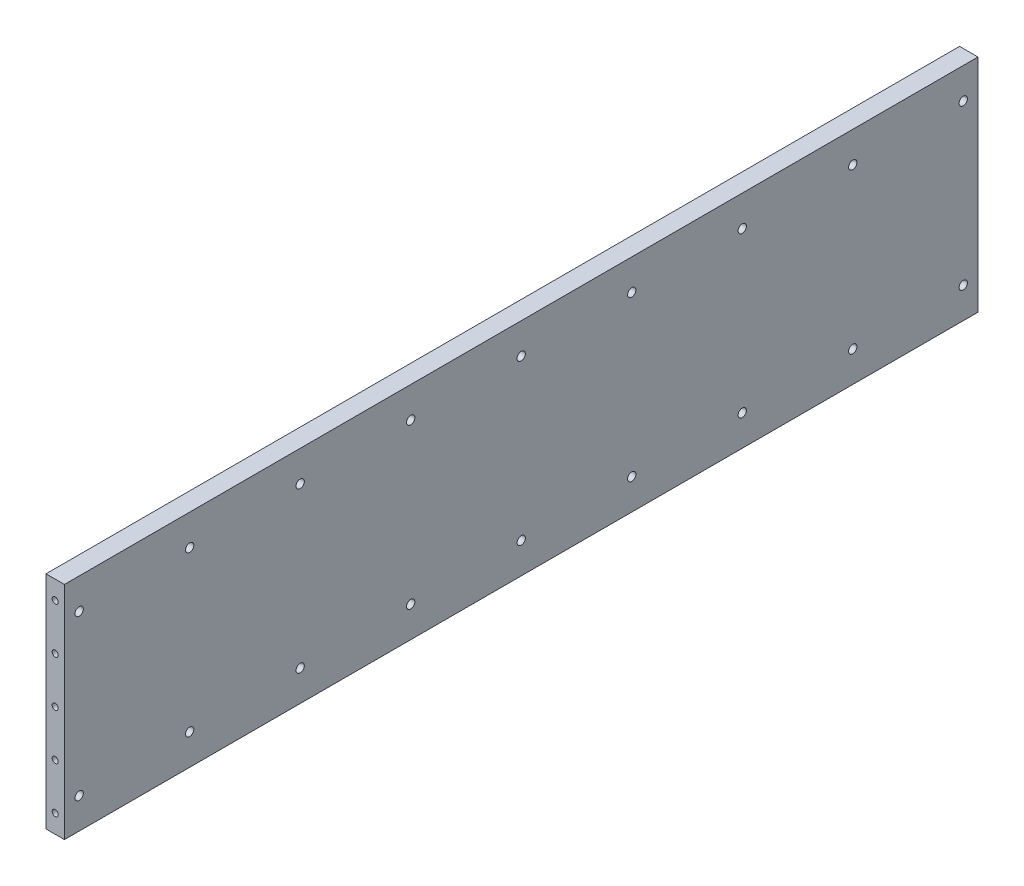
SolidWorks part; units mm, degrees
ref_plane "Front Plane" through (0, 0, 0) normal (0, 0, 1) x (1, 0, 0)
ref_plane "Top Plane" through (0, 0, 0) normal (0, 1, 0) x (1, 0, 0)
ref_plane "Right Plane" through (0, 0, 0) normal (1, 0, 0) x (0, 0, -1)
sketch "Sketch2" plane through (0, 0, 0) normal (0, 0, 1) x (1, 0, 0)
  line L0 (-10, 0) -> (0, 0)
  line L3 (0, 0) -> (0, -120)
  line L4 (0, -120) -> (-10, -120)
  line L5 (-10, -120) -> (-10, 0)
  dimension "D1" = 120
  dimension "D2" = 10
extrude "Boss-Extrude1" add sketch "Sketch2" along normal blind 496
sketch "Sketch3" plane through (0, 0, 496) normal (0, 0, 1) x (1, 0, 0)
  line L0 (-5, 0) -> (-5, -120) construction
  line L1 (0, 0) -> (-10, 0) construction
  line L2 (-10, -120) -> (0, -120) construction
  line L3 (-10, -60) -> (0, -60) construction
  line L4 (-10, 0) -> (-10, -120) construction
  line L5 (0, -120) -> (0, 0) construction
  point P12 (-5, -60)
  point P13 (-5, -110)
  point P14 (-5, -35)
  point P15 (-5, -10)
  point P16 (-5, -85)
  dimension "D1" = 3
hole_wizard "M4 Tapped Hole1" positions "3DSketch1" profile "Sketch4" tap size "M4" standard "ISO"
sketch3d "3DSketch1"
  point P0 (-5, -10, 496)
  point P3 (-5, -35, 496)
  point P6 (-5, -60, 496)
  point P9 (-5, -85, 496)
  point P12 (-5, -110, 496)
sketch "Sketch4" plane through (-5, -10, 496) normal (1, 0, 0) x (0, -1, 0)
  line L0 (0, 0) -> (0, 15.0914)
  line L1 (0, 15.0914) -> (1.65, 14.1)
  line L2 (1.65, 14.1) -> (1.65, 0)
  line L5 (1.65, 0) -> (0, 0)
  line L10 (0, 15.0914) -> (-1.65, 14.1) construction
  line L11 (0, -6.35) -> (0, 107.95) construction
  dimension "Tap Drill Dia." = 3.3
  dimension "Tap Drill Depth" = 14.1
  dimension "Drill Angle" = 118
sketch "Sketch5" plane through (0, 0, 0) normal (0, 0, -1) x (-1, 0, 0)
  line L0 (5, 0) -> (5, -120) construction
  line L1 (0, 0) -> (10, 0) construction
  line L2 (10, -120) -> (0, -120) construction
  line L3 (10, -60) -> (0, -60) construction
  point P10 (5, -60)
  point P11 (5, -85)
  point P12 (5, -35)
  point P13 (5, -10)
  point P14 (5, -110)
  dimension "D1" = 3
hole_wizard "M4 Tapped Hole2" positions "3DSketch2" profile "Sketch6" tap size "M4" standard "ISO"
sketch3d "3DSketch2"
  point P0 (-5, -10, 0)
  point P3 (-5, -35, 0)
  point P6 (-5, -60, 0)
  point P9 (-5, -85, 0)
  point P12 (-5, -110, 0)
sketch "Sketch6" plane through (-5, -10, 0) normal (1, 0, 0) x (0, 1, 0)
  line L0 (0, 0) -> (0, 15.0914)
  line L1 (0, 15.0914) -> (1.65, 14.1)
  line L2 (1.65, 14.1) -> (1.65, 0)
  line L5 (1.65, 0) -> (0, 0)
  line L10 (0, 15.0914) -> (-1.65, 14.1) construction
  line L11 (0, -6.35) -> (0, 107.95) construction
  dimension "Tap Drill Dia." = 3.3
  dimension "Tap Drill Depth" = 14.1
  dimension "Drill Angle" = 118
sketch "Sketch7" plane through (0, 0, 0) normal (1, 0, 0) x (0, 0, -1)
  line L0 (-496, -60) -> (0, -60) construction
  line L1 (0, 0) -> (0, -120) construction
  line L2 (-496, -16.7) -> (0, -16.7) construction
  line L3 (-496, 0) -> (-496, -120) construction
  line L4 (-496, 0) -> (0, 0) construction
  point P11 (-488, -16.7)
  point P12 (-8, -103.3)
  point P13 (-428, -16.7)
  point P14 (-368, -16.7)
  point P15 (-308, -16.7)
  point P16 (-248, -16.7)
  point P17 (-188, -16.7)
  point P18 (-128, -16.7)
  point P19 (-68, -16.7)
  point P20 (-8, -16.7)
  point P21 (-68, -103.3)
  point P22 (-128, -103.3)
  point P23 (-188, -103.3)
  point P24 (-248, -103.3)
  point P25 (-308, -103.3)
  point P26 (-368, -103.3)
  point P27 (-428, -103.3)
  point P28 (-488, -103.3)
  dimension "D1" = 16.7
  dimension "D2" = 8
  dimension "D3" = 9
hole_wizard "Ø4.5 (4.5) Diameter Hole1" positions "3DSketch3" profile "Sketch8" hole size "Ø4.5" standard "ISO" end condition through all
sketch3d "3DSketch3"
  point P0 (0, -16.7, 488)
  point P3 (0, -16.7, 428)
  point P6 (0, -16.7, 368)
  point P9 (0, -16.7, 308)
  point P12 (0, -16.7, 248)
  point P15 (0, -16.7, 188)
  point P18 (0, -16.7, 128)
  point P21 (0, -16.7, 68)
  point P24 (0, -16.7, 8)
  point P27 (0, -103.3, 8)
  point P30 (0, -103.3, 68)
  point P33 (0, -103.3, 128)
  point P36 (0, -103.3, 188)
  point P39 (0, -103.3, 248)
  point P42 (0, -103.3, 308)
  point P45 (0, -103.3, 368)
  point P48 (0, -103.3, 428)
  point P51 (0, -103.3, 488)
sketch "Sketch8" plane through (0, -16.7, 488) normal (0, 1, 0) x (0, 0, -1)
  line L0 (0, 0) -> (0, 10)
  line L1 (0, 10) -> (2.25, 10)
  line L2 (2.25, 10) -> (2.25, 0)
  line L5 (2.25, 0) -> (0, 0)
  line L11 (0, -6.35) -> (0, 107.95) construction
  dimension "Thru Hole Dia." = 4.5
  dimension "Thru Hole Depth" = 10
